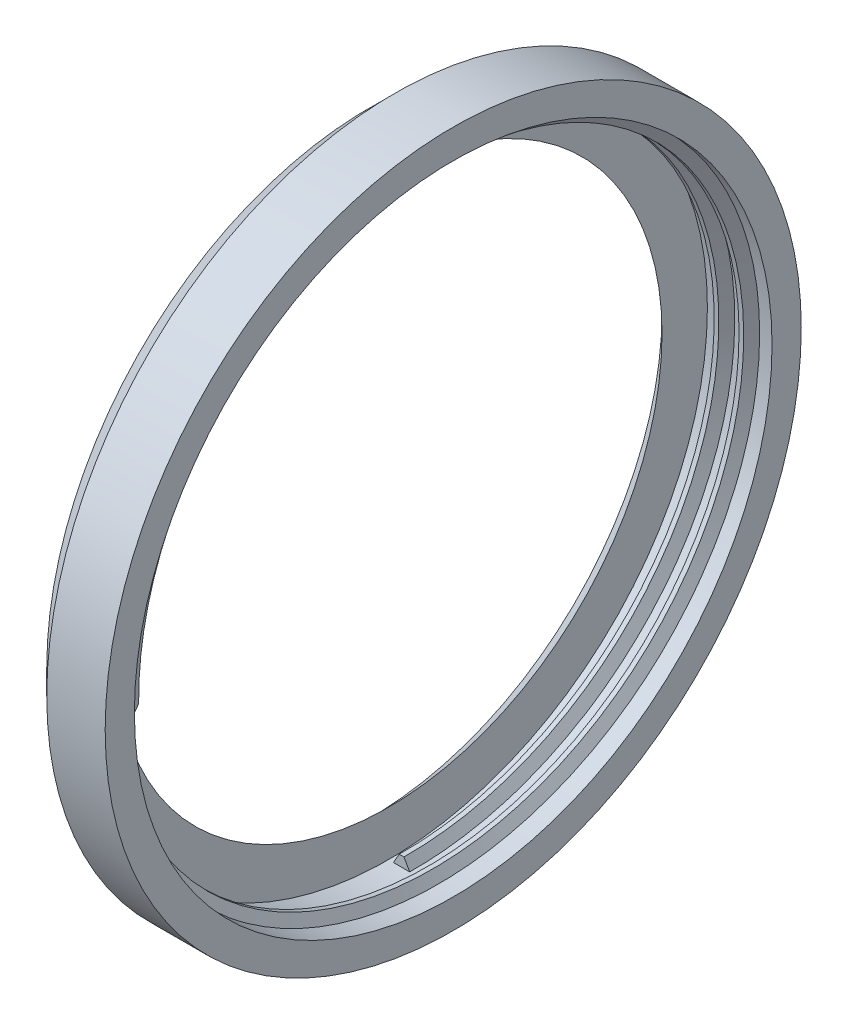
SolidWorks part; units mm, degrees
ref_plane "Front Plane" through (0, 0, 0) normal (0, 0, 1) x (1, 0, 0)
ref_plane "Top Plane" through (0, 0, 0) normal (0, 1, 0) x (1, 0, 0)
ref_plane "Right Plane" through (0, 0, 0) normal (1, 0, 0) x (0, 0, -1)
sketch "Sketch1" plane through (0, 0, 0) normal (1, 0, 0) x (0, 0, -1)
  circle A0 centre (0, 0) radius 22
  circle A1 centre (0, 0) radius 28
  dimension "D1" = 44
  dimension "D2" = 56
extrude "Boss-Extrude1" add sketch "Sketch1" along normal blind 1.5
sketch "Sketch2" plane through (1.5, 0, 0) normal (1, 0, 0) x (0, 0, -1)
  circle A2 centre (0, 0) radius 25.65
  circle A3 centre (0, 0) radius 25.65
  circle M2 centre (0, 0) radius 28
  dimension "D1" = 2.35
extrude "Boss-Extrude2" add sketch "Sketch2" along normal blind 5.2 contours A3 M2 region at (1.5, 0, 27.208)
thread "Thread1" pitch 1.5 method extrude profile "Thread Profile1" start angle 0, offset 0, length 3.5, pitch 2, diameter 51.3
ref_plane "Plane1" through (6.7, 0, 25.65) normal (0, -1, 0) x (0, 0, 1)
sketch "Thread Profile1" plane through (6.7, 0, 25.65) normal (0, -1, 0) x (0, 0, 1)
  line L0 (0, 0) -> (0, 1.5) construction
  line L11 (0, 0) -> (0, 1.3125)
  line L12 (0, 1.3125) -> (-0.8119, 0.8437)
  line L13 (-0.8119, 0.8437) -> (-0.8119, 0.4687)
  line L15 (-0.8119, 0.4687) -> (0, 0)
  line L17 (-0.8119, 0.6562) -> (0, 0.6562) construction
  point P2 (0, 0)
  dimension "Pitch" = 1.5
  dimension "Profile_Angle" = 60
  dimension "Profile_Land" = 0.375
  dimension "Profile_Height" = 0.8119
chamfer "Chamfer1" distance 2 angle 45 1 edges at (0, 0, -28)
chamfer "Chamfer2" distance 1.5 angle 45 1 edges at (0, 0, -22)
